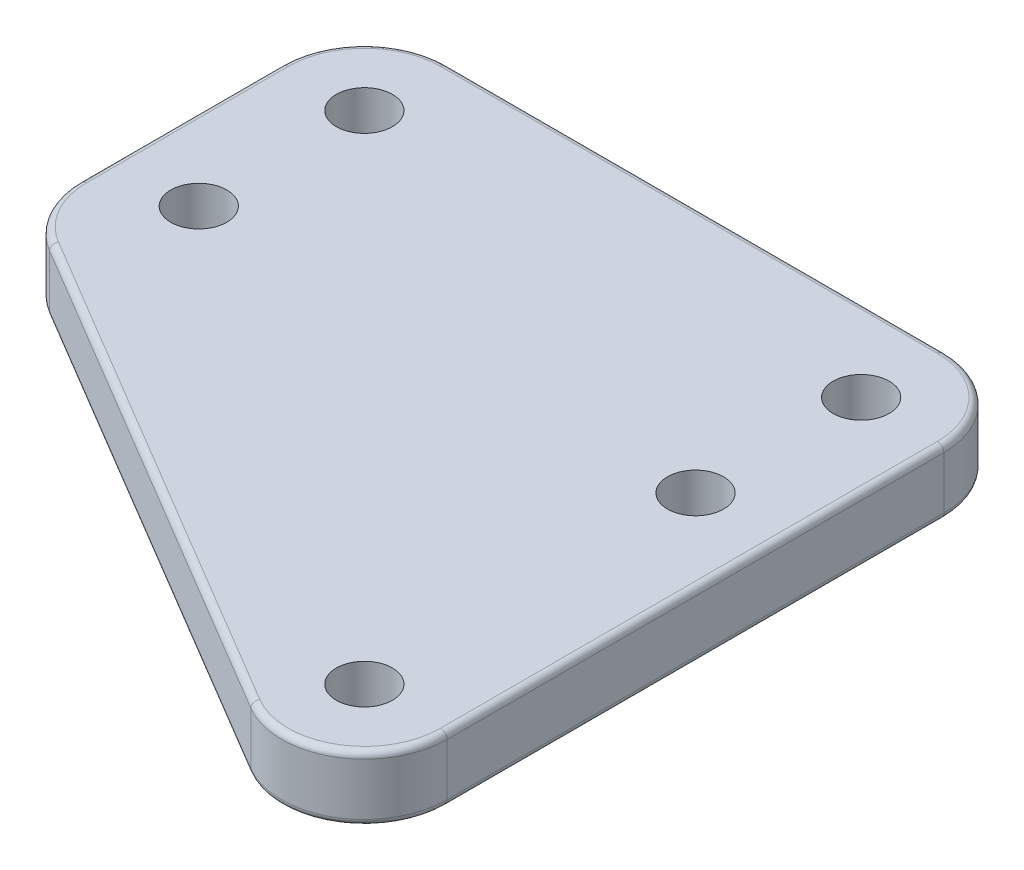
SolidWorks part; units mm, degrees
ref_plane "Front Plane" through (0, 0, 0) normal (0, 0, 1) x (1, 0, 0)
ref_plane "Top Plane" through (0, 0, 0) normal (0, 1, 0) x (1, 0, 0)
ref_plane "Right Plane" through (0, 0, 0) normal (1, 0, 0) x (0, 0, -1)
sketch "Sketch1" plane through (0, 0, 0) normal (0, 1, 0) x (1, 0, 0)
  line L0 (-44.45, -6.35) -> (-6.35, -6.35) construction
  line L1 (0, 0) -> (-50.8, 0)
  line L2 (0, 0) -> (0, -25.4)
  line L3 (0, -25.4) -> (-50.8, -25.4)
  line L4 (-50.8, 0) -> (-50.8, -25.4)
  line L5 (-44.45, -6.35) -> (-44.45, -19.05) construction
  line L6 (-50.8, -25.4) -> (-6.35, -51.8383)
  line L7 (0, -25.4) -> (0, -51.8383)
  line L8 (-6.35, -44.45) -> (-6.35, -51.8383) construction
  line L9 (0, -51.8383) -> (-6.35, -51.8383)
  circle A0 centre (-44.45, -6.35) radius 2.15
  circle A1 centre (-6.35, -6.35) radius 2.15
  circle A2 centre (-6.35, -19.05) radius 2.15
  circle A3 centre (-44.45, -19.05) radius 2.15
  circle A4 centre (-6.35, -44.45) radius 2.15
  circle A5 centre (-28.0881, -44.45) radius 4.7625
  dimension "D5" = 4.3
  dimension "D13" = 9.525
  dimension "D1" = 50.8
  dimension "D2" = 25.4
  dimension "D3" = 6.35
  dimension "D4" = 6.35
  dimension "D8" = 38.1
  dimension "D9" = 12.7
  dimension "D10" = 25.4
  dimension "D11" = 38.1
  dimension "D12" = 6.35
  dimension "D14" = 21.7381
  dimension "D6" = 2
  dimension "D7" = 2
extrude "Boss-Extrude1" add sketch "Sketch1" along normal blind 5 contours L1 L4 L3 L2 A3 A2 A1 A0 | L6 L3 A4 region at (-25.4, 0, 12.7) region at (-17.3806, 0, 35.0105)
fillet "Fillet1" radius 6.35 4 edges at (0, 2.5, 0) (-50.8, 2.5, 0) (-50.8, 2.5, 25.4) (0, 2.5, 51.8383)
fillet "Fillet2" radius 6.35 1 edges at (-6.35, 2.5, 51.8383)
fillet "Fillet3" radius 0.5 16 edges at (-49.9698, 0, 24.9278) (-50.8, 0, 14.0693) (-48.9401, 0, 1.8599) (-25.4, 0, 0) (-1.8599, 0, 1.8599) (0, 0, 25.4) (-3.2108, 0, 49.9698) (-49.9698, 5, 24.9278) (-50.8, 5, 14.0693) (-48.9401, 5, 1.8599) (-25.4, 5, 0) (-1.8599, 5, 1.8599) (0, 5, 25.4) (-3.2108, 5, 49.9698) (-28.6461, 0, 38.5769) (-28.6461, 5, 38.5769)
